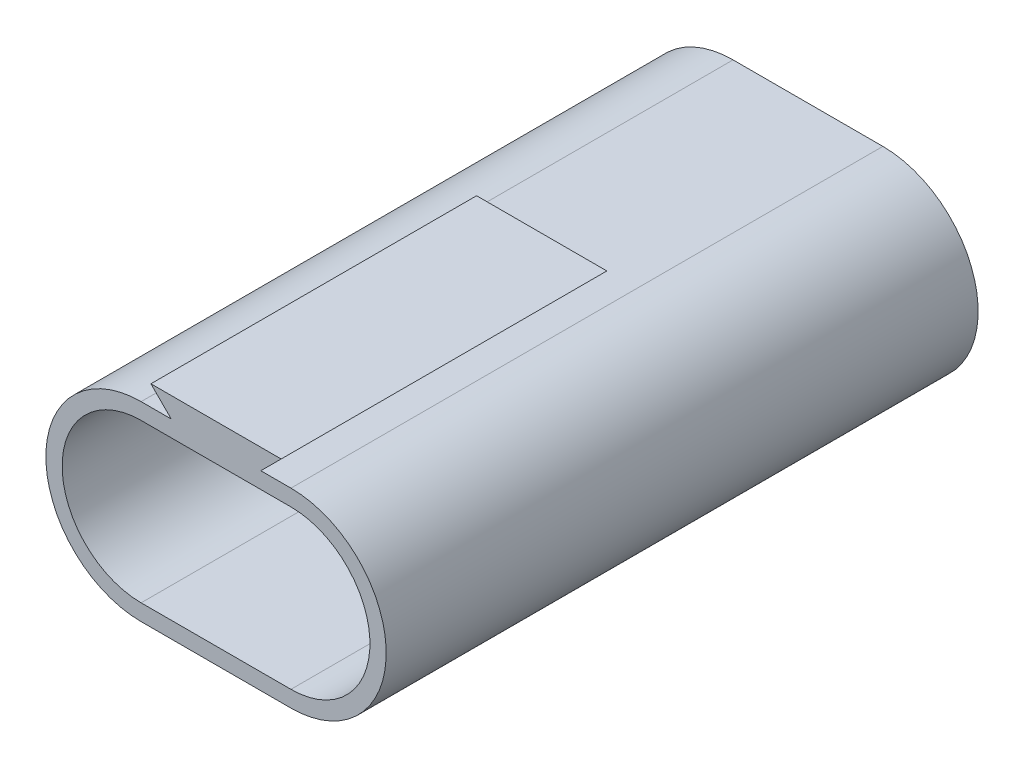
SolidWorks part; units mm, degrees
ref_plane "Ön Düzlem" through (0, 0, 0) normal (0, 0, 1) x (1, 0, 0)
ref_plane "Üst Düzlem" through (0, 0, 0) normal (0, 1, 0) x (1, 0, 0)
ref_plane "Sağ Düzlem" through (0, 0, 0) normal (1, 0, 0) x (0, 0, -1)
sketch "Çizim1" plane through (0, 0, 0) normal (0, 0, 1) x (1, 0, 0)
  line L0 (0, 0) -> (18.4, 0) construction
  line L1 (0, 9.2) -> (18.4, 9.2)
  line L2 (0, -9.2) -> (18.4, -9.2)
  line L3 (0, 9.7) -> (18.4, 9.7)
  line L4 (0, -9.7) -> (18.4, -9.7)
  line L5 (0, 11.7) -> (18.4, 11.7)
  line L6 (0, -11.7) -> (18.4, -11.7)
  arc A0 (0, 9.2) -> (0, -9.2) centre (0, 0) ccw
  arc A1 (18.4, -9.2) -> (18.4, 9.2) centre (18.4, 0) ccw
  arc A2 (18.4, -9.7) -> (18.4, 9.7) centre (18.4, 0) ccw
  arc A3 (0, 9.7) -> (0, -9.7) centre (0, 0) ccw
  arc A4 (18.4, -11.7) -> (18.4, 11.7) centre (18.4, 0) ccw
  arc A5 (0, 11.7) -> (0, -11.7) centre (0, 0) ccw
  point P3 (9.2, 0)
  dimension "D1" = 9.2
  dimension "D2" = 18.4
  dimension "D3" = 0.5
  dimension "D4" = 2
extrude "Yükseklik-Ekstrüzyon1" add sketch "Çizim1" along normal blind 70.2 contours L5 A5 L6 A4 A3 L3 A2 L4 region at (9.2, 11.221, 0)
sketch "Çizim2" plane through (0, 0, 0) normal (0, 0, -1) x (-1, 0, 0)
  line L2 (0, 11.7) -> (-18.4, 11.7)
  line L3 (-18.4, -11.7) -> (0, -11.7)
  line L4 (0, 11.7) -> (-18.4, 11.7)
  line L5 (-18.4, -11.7) -> (0, -11.7)
  arc A2 (-18.4, 11.7) -> (-18.4, -11.7) centre (-18.4, 0) ccw
  arc A3 (0, -11.7) -> (0, 11.7) centre (0, 0) ccw
  arc A4 (-18.4, 11.7) -> (-18.4, -11.7) centre (-18.4, 0) ccw
  arc A5 (0, -11.7) -> (0, 11.7) centre (0, 0) ccw
  dimension "D1" = 0
extrude "Yükseklik-Ekstrüzyon2" add sketch "Çizim2" along normal blind 2.5
sketch "Çizim8" plane through (0, 0, 70.2) normal (0, 0, 1) x (1, 0, 0)
  line L0 (14.7, 11.7) -> (3.7, 11.7)
  line L1 (0, 11.7) -> (18.4, 11.7) construction
  line L2 (3.7, 11.7) -> (1.2, 14.2)
  line L3 (1.2, 14.2) -> (17.2, 14.2)
  line L4 (17.2, 14.2) -> (14.7, 11.7)
  point P5 (9.2, 11.7)
  point P8 (9.2, 11.7)
  dimension "D1" = 11
  dimension "D2" = 16
  dimension "D3" = 135
  dimension "D4" = 135
extrude "Yükseklik-Ekstrüzyon5" add sketch "Çizim8" against normal blind 40
chamfer "Pah1" distance 2.5 angle 45 1 edges at (9.2, 11.7, 30.2)
sketch "Çizim9" plane through (0, 0, -2.5) normal (0, 0, -1) x (-1, 0, 0)
  line L0 (0, 0) -> (-18.4, 0) construction
  line L1 (0, -3) -> (-18.4, -3)
  line L2 (0, 3) -> (-18.4, 3)
  arc A0 (0, -3) -> (0, 3) centre (0, 0) ccw
  arc A1 (-18.4, 3) -> (-18.4, -3) centre (-18.4, 0) ccw
  point P4 (-9.2, 0)
  dimension "D1" = 6
extrude "Kes-Ekstrüzyon1" cut sketch "Çizim9" against normal blind 10
